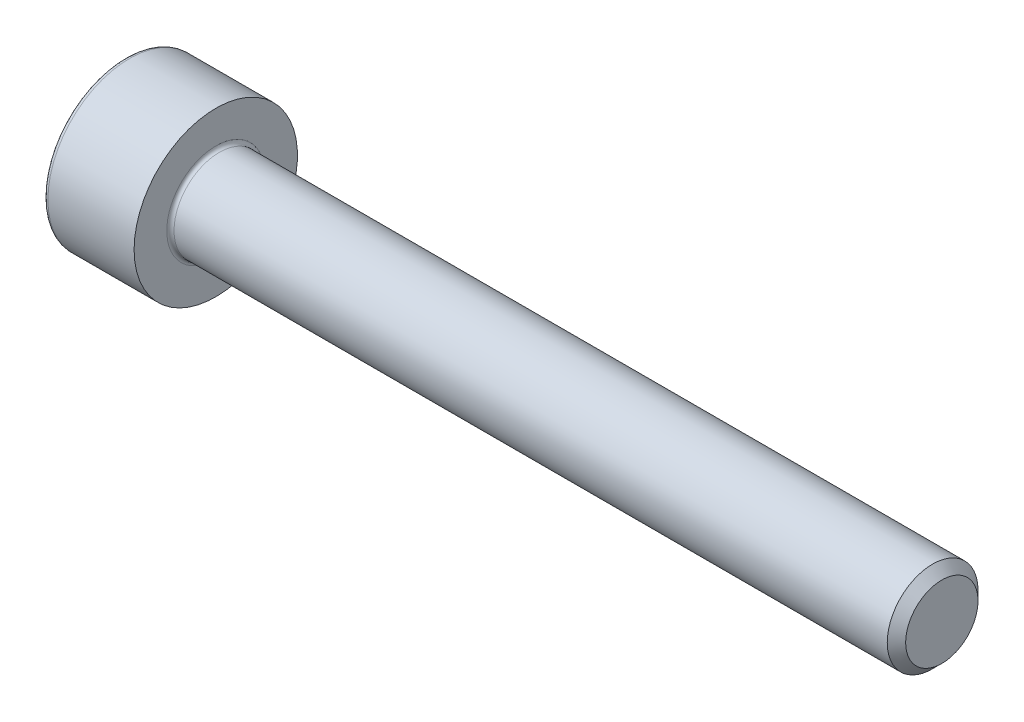
SolidWorks part; units mm, degrees
revolve "Base-Revolve" add sketch "BodySke"
sketch "BodySke" plane through (0, 0, 0) normal (0, 0, 1) x (1, 0, 0)
  line L0 (0, 0) -> (0, 2.25)
  line L1 (0, 2.25) -> (2.5, 2.25)
  line L2 (2.5, 2.25) -> (2.5, 1.25)
  line L3 (2.5, 1.25) -> (22.2465, 1.25)
  line L4 (22.5, 0.9965) -> (22.5, 0)
  line L5 (22.5, 0) -> (0, 0)
  line L6 (-31.75, 0) -> (127, 0) construction
  line L8 (22.5, 0.9965) -> (22.2465, 1.25)
  line L10 (22.5, -0.9965) -> (22.2465, -1.25) construction
  line L11 (2.95, 9.525) -> (2.95, 3.175) construction
  line L12 (2.5, 9.525) -> (2.5, 3.175) construction
  line L13 (-37.5, 9.525) -> (-37.5, 3.175) construction
  dimension "Diameter" = 2.5
  dimension "Head_dia" = 4.5
cosmetic thread "ThreadCosmetic" [suppressed]
fillet "Fillet1" radius 0.1 1 edges at (2.5, 0, 1.25)
fillet "Fillet2" radius 0.125 1 edges at (0, 0, 2.25)
ref_plane "Plane1" through (0, 0, 0) normal (0, 0, 1) x (1, 0, 0)
ref_plane "Plane2" through (0, 0, 0) normal (0, 1, 0) x (1, 0, 0)
ref_plane "Plane3" through (0, 0, 0) normal (1, 0, 0) x (0, 0, -1)
sketch "Sketch2" plane through (0, 0, 0) normal (0, 0, 1) x (1, 0, 0)
  line L0 (0, 1.0225) -> (1.1, 1.0225)
  line L1 (1.1, 1.0225) -> (1.6903, 0)
  line L2 (-31.75, 0) -> (127, 0) construction
  line L3 (1.6903, 0) -> (0, 0)
  line L4 (0, 0) -> (0, 1.0225)
  line L6 (0, 0) -> (47.625, 0) construction
  dimension "D1" = 1.0225
  dimension "D2" = 60
revolve "Hex-PreBroach" cut sketch "Sketch2" angle 360 about L6
sketch "Sketch3" plane through (0, 0, 0) normal (-1, 0, 0) x (0, 0.5, 0.866)
  line L0 (0.5903, 1.0225) -> (-0.5903, 1.0225)
  line L1 (-0.5903, 1.0225) -> (-1.1807, 0)
  line L2 (0.5903, 1.0225) -> (1.1807, 0)
  line L3 (0.5903, -1.0225) -> (1.1807, 0)
  line L4 (0.5903, -1.0225) -> (-0.5903, -1.0225)
  line L5 (-0.5903, -1.0225) -> (-1.1807, 0)
  dimension "D1" = 1.0225
  dimension "D2" = 1.0225
extrude "Hex" cut sketch "Sketch3" against normal blind 1.1
sketch "ThdSchSke" plane through (0, 0, 0) normal (0, 0, 1) x (1, 0, 0)
  line L0 (3.85, -0.9965) -> (3.6725, -1.25)
  line L1 (3.85, -0.9965) -> (4.0275, -1.25)
  line L2 (4.0275, -1.25) -> (4.0275, -1.5625)
  line L3 (-3.175, 0) -> (5.1513, 0) construction
  line L4 (0, 2.125) -> (0, -2.125) construction
  line L5 (4.0275, -1.5625) -> (3.6725, -1.5625)
  line L6 (3.6725, -1.5625) -> (3.6725, -1.25)
  dimension "Diameter" = 2.5
  dimension "Thread_minor" = 1.993
  dimension "Start" = 3.85
revolve "ThreadSchematic" [suppressed] cut sketch "ThdSchSke" angle 360 about L3
pattern_linear "ThdSchPat" [suppressed]
equation "\"D2@Sketch3\" = \"Hex_size@Sketch3\" / 2"
equation "\"D1@Sketch3\" = \"Hex_size@Sketch3\" / 2"
equation "\"D1@Sketch2\" = \"Hex_size@Sketch3\" / 2"
equation "\"Thread_minor@ThreadCosmetic\"  =  \"Minor_dia@BodySke\""
equation "\"Depth@Sketch2\" =  \"Key_eng@Hex\""
equation "\"Thread_length@ThreadCosmetic\" = ((sgn( (\"Length@BodySke\" - \"Advance@BodySke\" * 3.0) - \"Thread_nom@BodySke\" )-1)*( (\"Length@BodySke\" - \"Advance@BodySke\" * 3.0) - \"Thread_nom@BodySke\" ))/-2+ \"Thread_nom@BodySke\""
equation "\"Thread_minor@ThdSchSke\" = \"Minor_dia@BodySke\""
equation "\"Diameter@ThdSchSke\" = \"Diameter@BodySke\""
equation "\"Overcut@ThdSchSke\" = \"Diameter@BodySke\" * 1.25"
equation "\"Start@ThdSchSke\" = \"Head_ht@BodySke\" + \"Length@BodySke\" - \"Thread_length@ThreadCosmetic\"  '---Non-countersunk---"
equation "\"Num_threads@ThdSchPat\" = int( \"Thread_length@ThreadCosmetic\" / \"Advance@BodySke\" + 0.999 )  + 1"
equation "\"Advance@ThdSchPat\" = \"Thread_length@ThreadCosmetic\" /  (\"Num_threads@ThdSchPat\" - 1) 'relax it"
equation "\"Num_threads@ThdSchPat\" = \"Num_threads@ThdSchPat\" - sgn( \"Num_threads@ThdSchPat\" - 1) '---chamfered tips only---"
